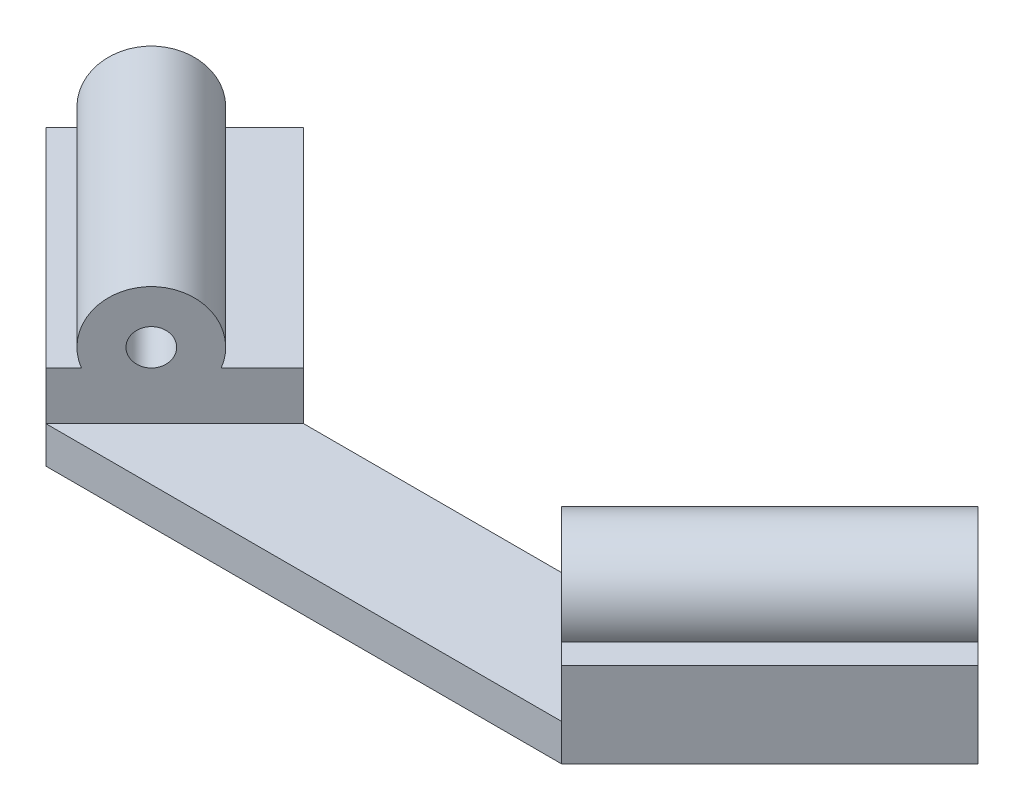
SolidWorks part; units mm, degrees
ref_plane "Front Plane" through (0, 0, 0) normal (0, 0, 1) x (1, 0, 0)
ref_plane "Top Plane" through (0, 0, 0) normal (0, 1, 0) x (1, 0, 0)
ref_plane "Right Plane" through (0, 0, 0) normal (1, 0, 0) x (0, 0, -1)
sketch "Trapezoid1" plane through (0, 0, 0) normal (0, 1, 0) x (1, 0, 0)
  line L0 (-114.3356, -37.1761) -> (-96.8356, -19.6761)
  line L1 (-96.8356, -19.6761) -> (-61.8356, -19.6761)
  line L3 (-114.3356, -37.1761) -> (-44.3356, -37.1761)
  line L7 (-44.3356, -37.1761) -> (-61.8356, -19.6761)
  point P0 (0, 0)
  dimension "D1" = 45
  dimension "D2" = 45
  dimension "D3" = 70
  dimension "D4" = 35
extrude "Boss-Extrude1" add sketch "Trapezoid1" along normal blind 5
sketch "AntennaHolster1" plane through (-40.7559, 0, 40.7559) normal (0.7071, 0, -0.7071) x (-0.7071, 0, -0.7071)
  line L1 (5.0626, 0) -> (29.8113, 0)
  line L2 (5.0626, 0) -> (5.0626, 11.55)
  line L3 (5.0626, 11.55) -> (29.8113, 11.55)
  line L4 (29.8113, 0) -> (29.8113, 11.55)
  circle A0 centre (15.7076, 13.9863) radius 2.4363
  arc A1 (22.4231, 11.55) -> (8.9921, 11.55) centre (15.7076, 13.9863) ccw
  line M6 (5.0626, 0) -> (29.8113, 0)
  line M7 (29.8113, 0) -> (29.8113, 5)
  line M8 (29.8113, 5) -> (5.0626, 5)
  line M9 (5.0626, 5) -> (5.0626, 0)
extrude "Boss-Extrude2" add sketch "AntennaHolster1" along normal blind 40 contours M9 M6 M7 M8 | L4 L3 L2 M8 | L3 A1 A0 region at (-53.0856, 2.5, 28.4261) region at (-53.0856, 8.275, 28.4261) region at (-51.8628, 20.958, 29.6489)
sketch "AntennaHolster2" plane through (-38.5798, 0, -38.5798) normal (-0.7071, 0, -0.7071) x (-0.7071, 0, 0.7071)
  line L0 (107.135, 5) -> (107.135, 0) construction
  line L1 (82.3862, 0) -> (107.135, 0)
  line L2 (82.3862, 0) -> (82.3862, 11.55)
  line L3 (82.3862, 11.55) -> (107.135, 11.55)
  line L4 (107.135, 0) -> (107.135, 11.55)
  circle A0 centre (97.0214, 13.9862) radius 2.4362
  arc A1 (103.7369, 11.55) -> (90.3059, 11.55) centre (97.0214, 13.9862) ccw
  line M6 (82.3862, 0) -> (107.135, 0)
  line M7 (107.135, 0) -> (107.135, 5)
  line M8 (107.135, 5) -> (82.3862, 5)
  line M9 (82.3862, 5) -> (82.3862, 0)
extrude "Boss-Extrude3" add sketch "AntennaHolster2" along normal blind 40 contours M9 M6 M7 M8 | L4 L3 L2 M8 | L3 A1 A0 region at (-105.5856, 2.5, 28.4261) region at (-105.5856, 8.275, 28.4261) region at (-107.1843, 20.958, 30.0247)
